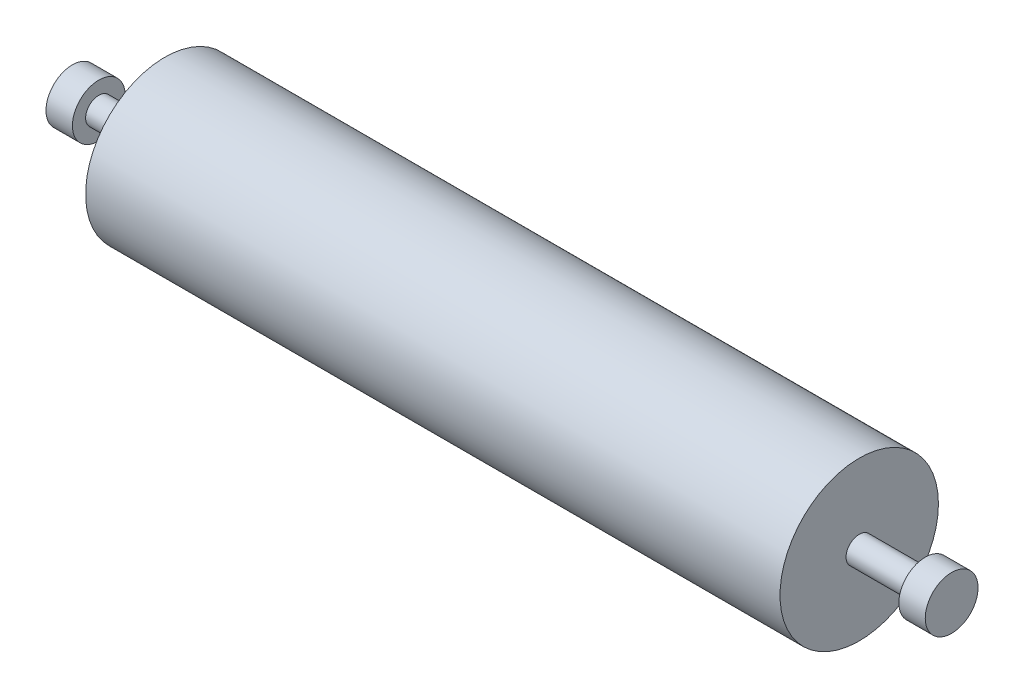
SolidWorks part; units mm, degrees
ref_plane "Front Plane" through (0, 0, 0) normal (0, 0, 1) x (1, 0, 0)
ref_plane "Top Plane" through (0, 0, 0) normal (0, 1, 0) x (1, 0, 0)
ref_plane "Right Plane" through (0, 0, 0) normal (1, 0, 0) x (0, 0, -1)
sketch "Sketch1" plane through (0, 0, 0) normal (1, 0, 0) x (0, 0, -1)
  circle A0 centre (0, 0) radius 38.1
extrude "Boss-Extrude1" add sketch "Sketch1" along normal blind 167.005 and the other way blind 167.005
sketch "Sketch2" plane through (-167.005, 0, 0) normal (-1, 0, 0) x (0, 0, 1)
  circle A0 centre (0, 0) radius 6.35
extrude "Boss-Extrude2" add sketch "Sketch2" along normal blind 31.75
sketch "Sketch3" plane through (-198.755, 0, 0) normal (-1, 0, 0) x (0, 0, 1)
  circle A0 centre (0, 0) radius 12.7
extrude "Boss-Extrude3" add sketch "Sketch3" along normal blind 12.7
mirror "Mirror1" about plane through (0, 0, 0) normal (1, 0, 0) of "Boss-Extrude2", "Boss-Extrude3"
